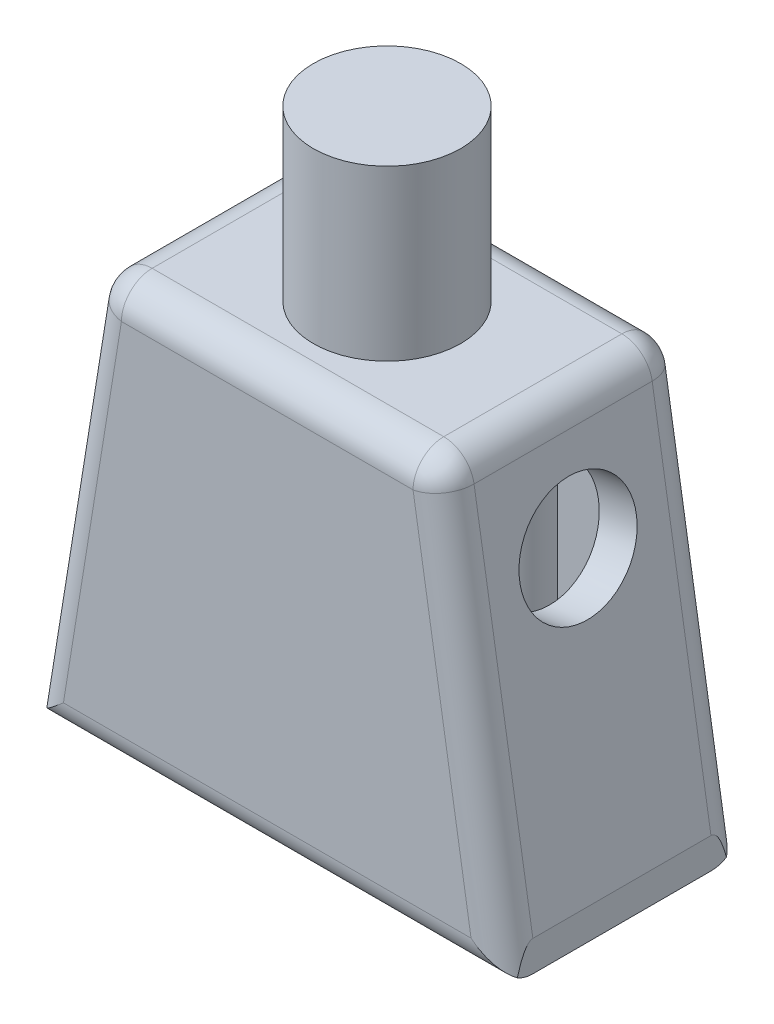
SolidWorks part; units mm, degrees
ref_plane "Front Plane" through (0, 0, 0) normal (0, 0, 1) x (1, 0, 0)
ref_plane "Top Plane" through (0, 0, 0) normal (0, 1, 0) x (1, 0, 0)
ref_plane "Right Plane" through (0, 0, 0) normal (1, 0, 0) x (0, 0, -1)
sketch "Sketch4" plane through (0, 0, 0) normal (0, 0, 1) x (1, 0, 0)
  line L0 (7.65, 0) -> (-7.65, 0)
  line L1 (-7.65, 0) -> (-7.65, 1)
  line L2 (-7.65, 1) -> (-5.6, 13.6992)
  line L3 (-5.6, 13.6992) -> (5.6, 13.6992)
  line L4 (5.6, 13.6992) -> (7.65, 1)
  line L5 (7.65, 1) -> (7.65, 0)
  point P7 (-8.8091, 13.6992)
  point P8 (0, 0)
  dimension "D1" = 15.3
  dimension "D2" = 11.2
  dimension "D3" = 1
  dimension "D4" = 80.83
extrude "Boss-Extrude1" add sketch "Sketch4" along normal mid plane 7.8
shell "Shell2" thickness 1.25 removed face at (0, 0, 0)
sketch "Sketch5" plane through (7.613, 1.229, 0) normal (0.9872, 0.1594, 0) x (0, 0, -1)
  line L0 (0, 8.7282) -> (-3.9, 8.7282) construction
  line L1 (-3.9, -0.2319) -> (-3.9, 12.6317) construction
  line L2 (0, 8.7282) -> (3.9, 8.7282) construction
  line L3 (3.9, -0.2319) -> (3.9, 12.6317) construction
  circle A0 centre (0, 8.7282) radius 1.9
  dimension "D1" = 3.8
  dimension "D2" = 8.7282
extrude "Cut-Extrude2" cut sketch "Sketch5" against normal blind 7.8
mirror "Mirror1" about plane through (0, 0, 0) normal (1, 0, 0) of "Cut-Extrude2"
fillet "Fillet1" radius 1 10 edges at (5.6, 13.6992, 0) (0, 13.6992, 3.9) (-5.6, 13.6992, 0) (0, 13.6992, -3.9) (6.625, 7.3496, 3.9) (6.625, 7.3496, -3.9) (-6.625, 7.3496, -3.9) (-6.625, 7.3496, 3.9) (0, 0, 3.9) (0, 0, -3.9)
sketch "Sketch6" plane through (0, 13.6992, 0) normal (0, 1, 0) x (1, 0, 0)
  circle A0 centre (0, 0) radius 2.4
  dimension "D1" = 4.8
extrude "Boss-Extrude2" add sketch "Sketch6" along normal blind 5.5
sketch "Sketch7" plane through (0, 12.4492, 0) normal (0, -1, 0) x (1, 0, 0)
  circle A0 centre (0, 0) radius 1.25
  dimension "D1" = 2.5
extrude "Cut-Extrude3" cut sketch "Sketch7" against normal blind 4.25
sketch "Sketch8" plane through (0, 0, 0) normal (0, -1, 0) x (1, 0, 0)
  line L0 (-1.5, -2.65) -> (-1.5, -1.25)
  line L1 (-6.4, -2.65) -> (6.4, -2.65) construction
  line L2 (4.5356, -2.65) -> (-4.5356, -2.65) construction
  line L3 (-2.9, -2.65) -> (-1.5, -2.65)
  arc A1 (-2.9, -2.65) -> (-1.5, -1.25) centre (-1.5, -2.65) cw
  dimension "D2" = 1.4
  dimension "D1" = 1.5
extrude "Boss-Extrude3" add sketch "Sketch8" against normal up to surface (12.4492 mm away) up to face at (1.25, 12.4492, 0)
mirror "Mirror2" about plane through (0, 0, 0) normal (1, 0, 0) of "Boss-Extrude3"
mirror "Mirror3" about plane through (0, 0, 0) normal (0, 0, 1) of "Mirror2"
